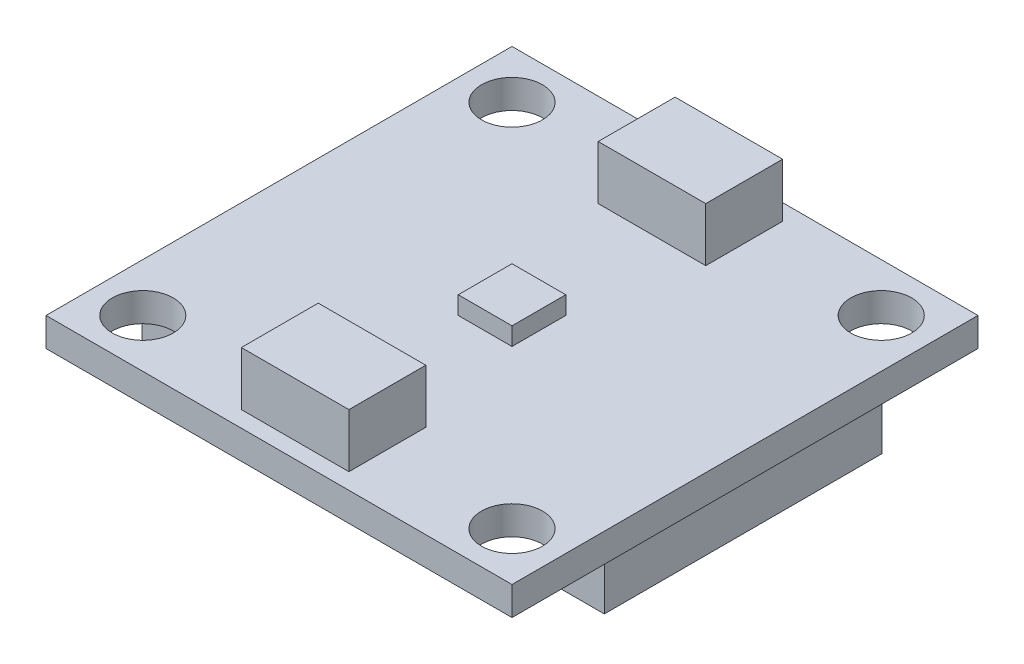
SolidWorks part; units mm, degrees
ref_plane "Front Plane" through (0, 0, 0) normal (0, 0, 1) x (1, 0, 0)
ref_plane "Top Plane" through (0, 0, 0) normal (0, 1, 0) x (1, 0, 0)
ref_plane "Right Plane" through (0, 0, 0) normal (1, 0, 0) x (0, 0, -1)
sketch "Sketch1" plane through (0, 0, 0) normal (0, 1, 0) x (1, 0, 0)
  line L0 (-12, 12) -> (-12, -12) construction
  line L1 (-13, 13) -> (13, 13)
  line L2 (-13, 13) -> (-13, -13)
  line L3 (-13, -13) -> (13, -13)
  line L4 (13, 13) -> (13, -13)
  line L5 (-13, 13) -> (13, -13) construction
  line L6 (-13, -13) -> (13, 13) construction
  line L11 (-12, -12) -> (12, -12) construction
  line L12 (12, 12) -> (12, -12) construction
  line L13 (-12, 12) -> (12, 12) construction
  circle A0 centre (-10.3, 10.3) radius 1.7
  circle A1 centre (10.3, 10.3) radius 1.7
  circle A2 centre (-10.3, -10.3) radius 1.7
  circle A3 centre (10.3, -10.3) radius 1.7
  point P0 (0, 0)
  point P18 (0, 0)
  dimension "D3" = 3.4
  dimension "D1" = 26
  dimension "D2" = 1
extrude "Boss-Extrude1" add sketch "Sketch1" along normal blind 1.6
sketch "Sketch2" plane through (0, 1.6, 0) normal (0, 1, 0) x (1, 0, 0)
  line L0 (-13, 0) -> (13, 0) construction
  line L1 (-13, 13) -> (-13, -13) construction
  line L2 (13, 13) -> (-13, 13) construction
  line L3 (-3, 12.1) -> (3, 12.1)
  line L4 (-3, 12.1) -> (-3, 7.81)
  line L5 (-3, 7.81) -> (3, 7.81)
  line L6 (3, 12.1) -> (3, 7.81)
  line L7 (-3, -7.81) -> (3, -7.81)
  line L8 (3, -12.1) -> (3, -7.81)
  line L9 (-3, -12.1) -> (3, -12.1)
  line L10 (-3, -12.1) -> (-3, -7.81)
  point P2 (0, 0)
  point P4 (0, 7.81)
  dimension "D1" = 6
  dimension "D2" = 4.29
  dimension "D3" = 0.9
extrude "Boss-Extrude2" add sketch "Sketch2" along normal blind 3
sketch "Sketch3" plane through (0, 0, 0) normal (0, -1, 0) x (1, 0, 0)
  line L1 (-12.9, 7.75) -> (-10.4, 7.75)
  line L2 (-12.9, 7.75) -> (-12.9, -7.75)
  line L3 (-12.9, -7.75) -> (-10.4, -7.75)
  line L4 (-10.4, 7.75) -> (-10.4, -7.75)
  line L5 (10.4, 7.75) -> (12.9, 7.75)
  line L6 (10.4, 7.75) -> (10.4, -7.75)
  line L7 (10.4, -7.75) -> (12.9, -7.75)
  line L8 (12.9, 7.75) -> (12.9, -7.75)
  line L10 (-10.4, 0) -> (10.4, 0) construction
  line L11 (13, 13) -> (13, -13) construction
  point P8 (-10.4, 0)
  point P9 (10.4, 0)
  point P13 (6.4351, 4.7923)
  point P14 (0, 0)
  point P15 (0, 0)
  point P16 (0, 0)
  dimension "D1" = 15.5
  dimension "D2" = 2.5
  dimension "D3" = 0.1
extrude "Boss-Extrude3" add sketch "Sketch3" along normal blind 2.5
sketch "Sketch4" plane through (0, 1.6, 0) normal (0, 1, 0) x (1, 0, 0)
  line L1 (-1.5, 1.5) -> (1.5, 1.5)
  line L2 (-1.5, 1.5) -> (-1.5, -1.5)
  line L3 (-1.5, -1.5) -> (1.5, -1.5)
  line L4 (1.5, 1.5) -> (1.5, -1.5)
  line L5 (-1.5, 1.5) -> (1.5, -1.5) construction
  line L6 (-1.5, -1.5) -> (1.5, 1.5) construction
  point P0 (0, 0)
  dimension "D1" = 3
extrude "Boss-Extrude4" add sketch "Sketch4" along normal blind 1
